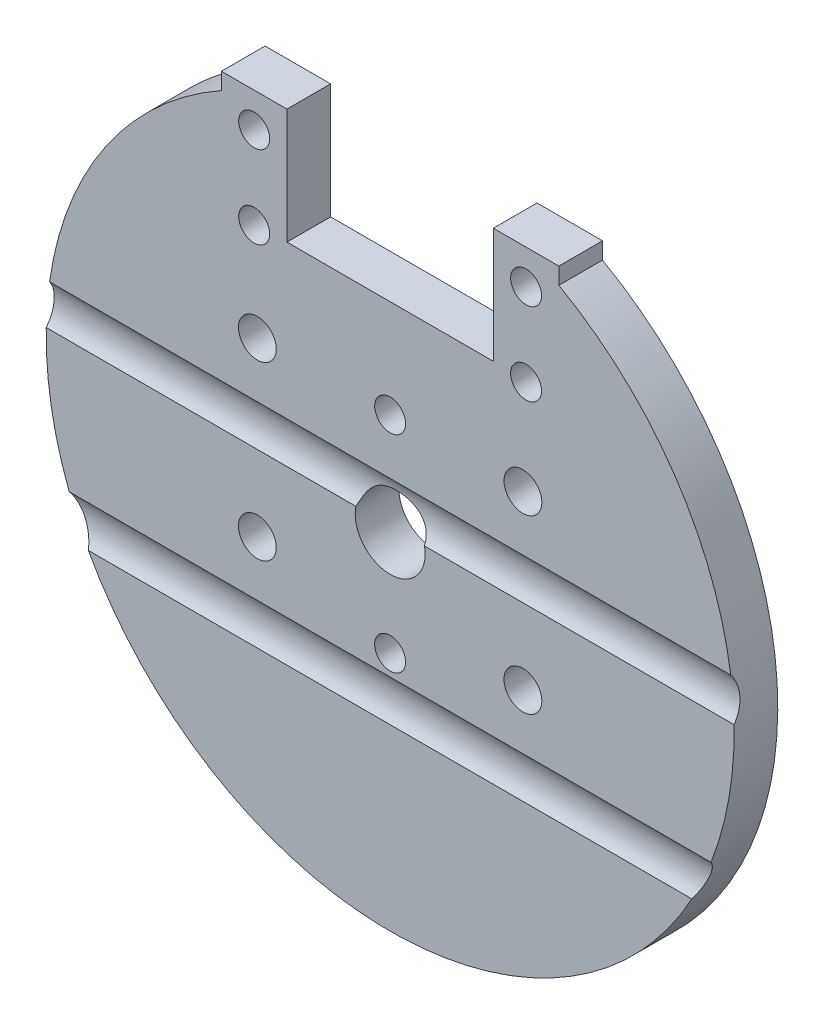
SolidWorks part; units mm, degrees
material "6061 Alloy"
ref_plane "Front Plane" through (0, 0, 0) normal (0, 0, 1) x (1, 0, 0)
ref_plane "Top Plane" through (0, 0, 0) normal (0, 1, 0) x (1, 0, 0)
ref_plane "Right Plane" through (0, 0, 0) normal (1, 0, 0) x (0, 0, -1)
sketch "Sketch1" plane through (0, 0, 0) normal (0, 0, 1) x (1, 0, 0)
  circle A0 centre (0, 0) radius 50
  dimension "D1" = 100
extrude "1/4" add sketch "Sketch1" along normal blind 6.35
sketch "Sketch2" plane through (0, 0, 6.35) normal (0, 0, 1) x (1, 0, 0)
  line L0 (0, 0) -> (0, 50) construction
  line L1 (-1.318, 74.311) -> (-1.318, 76.1424) construction
  line L3 (-15, 46) -> (-15, 29.25)
  line L4 (-15, 29.25) -> (15, 29.25)
  line L5 (15, 46) -> (15, 29.25)
  line L6 (0, 0) -> (0, 50) construction
  line L7 (-15, 37.625) -> (15, 37.625) construction
  line L8 (-30.7361, 76.1424) -> (28.1002, 76.1424)
  line L9 (-30.7361, 76.1424) -> (-30.7361, 46)
  line L10 (-30.7361, 46) -> (-15, 46)
  line L11 (28.1002, 76.1424) -> (28.1002, 46)
  line L12 (15, 46) -> (28.1002, 46)
  line L13 (-30.7361, 61.0712) -> (28.1002, 61.0712) construction
  circle A0 centre (0, 0) radius 50 construction
  point P6 (0, 37.625)
  point P130 (-1.318, 61.0712)
  dimension "D1" = 30
  dimension "D2" = 29.25
  dimension "D3" = 46
extrude "Cut-Extrude1" cut sketch "Sketch2" against normal up to surface (6.35 mm away) up to face at (50, 0, 0)
sketch "Sketch3" plane through (0, 0, 6.35) normal (0, 0, 1) x (1, 0, 0)
  line L1 (-15, 29.25) -> (-24.525, 29.25)
  line L2 (-15, 29.25) -> (-15, 46)
  line L3 (-15, 46) -> (-24.525, 46)
  line L4 (-24.525, 29.25) -> (-24.525, 46)
  line L5 (-19.7625, 46) -> (-19.7625, 29.25) construction
  line L6 (-15, 37.625) -> (-24.525, 37.625) construction
  line L7 (15, 29.25) -> (24.525, 29.25)
  line L8 (15, 29.25) -> (15, 46)
  line L9 (15, 46) -> (24.525, 46)
  line L10 (24.525, 29.25) -> (24.525, 46)
  line L11 (19.7625, 46) -> (19.7625, 29.25) construction
  line L12 (15, 37.625) -> (24.525, 37.625) construction
  point P168 (19.7625, 37.625)
  point P204 (-19.7625, 37.625)
  dimension "D1" = 9.525
  dimension "D2" = 9.525
  dimension "D3" = 46
extrude "Boss-Extrude2" add sketch "Sketch3" against normal up to surface (6.35 mm away) up to face at (0, 24.4167, 0)
sketch "Sketch4" plane through (0, 0, 6.35) normal (0, 0, 1) x (1, 0, 0)
  line L0 (-15, 35) -> (-24.525, 35) construction
  line L2 (-24.525, 46) -> (-24.525, 43.5721) construction
  line L3 (-19.7625, 41) -> (-19.7625, 35) construction
  line L4 (0, 0) -> (0, 50.3734) construction
  line L5 (-15, 46) -> (-15, 29.25) construction
  circle A0 centre (-19.7625, 41) radius 2.25
  circle A1 centre (-19.7625, 29) radius 2.25
  circle A2 centre (19.7625, 29) radius 2.25
  circle A3 centre (19.7625, 41) radius 2.25
  dimension "D1" = 4.5
  dimension "D2" = 6
  dimension "D3" = 35
extrude "M4_through" cut sketch "Sketch4" against normal up to surface (6.35 mm away) up to face at (0, 29.509, 0)
chamfer "Chamfer1" distance 2.5 angle 45 4 edges at (22.0125, 41, 0) (-17.5125, 29, 0) (-17.5125, 41, 0) (22.0125, 29, 0)
sketch "Sketch5" plane through (0, 0, 6.35) normal (0, 0, 1) x (1, 0, 0)
  circle A0 centre (0, 0) radius 5.08
  dimension "D1" = 10.16
extrude "Cut-Extrude2" cut sketch "Sketch5" against normal up to surface (6.35 mm away) up to face at (-15.0125, 29, 0)
sketch "Sketch6" plane through (0, 0, 6.35) normal (0, 0, 1) x (1, 0, 0)
  circle A0 centre (0, 0) radius 15 construction
  circle A1 centre (0, 15) radius 2.25
  circle A2 centre (0, -15) radius 2.25
  point P13 (0, 0)
  dimension "D1" = 30
  dimension "D2" = 4.5
  dimension "D3" = 2
extrude "M4_through2" cut sketch "Sketch6" against normal up to surface (6.35 mm away) up to face at (5.08, 0, 0)
sketch "Sketch7" plane through (0, 0, 6.35) normal (0, 0, 1) x (1, 0, 0)
  line L0 (0, 0) -> (0, 38.8961) construction
  line L1 (-19.3, 15) -> (-19.3, -10) construction
  circle A0 centre (-19.3, 15) radius 2.75
  circle A1 centre (-19.3, -10) radius 2.75
  circle A2 centre (19.3, -10) radius 2.75
  circle A3 centre (19.3, 15) radius 2.75
  circle A4 centre (0, 0) radius 30 construction
  point P11 (-19.3, 11.4777)
  dimension "D2" = 5.5
  dimension "D3" = 25
  dimension "D4" = 60
  dimension "D1" = 19.3
  dimension "D5" = 15
extrude "M5_through" cut sketch "Sketch7" against normal up to surface (6.35 mm away) up to face at (2.25, 15, 0)
sketch "Sketch8" plane through (0, 0, 0) normal (1, 0, 0) x (0, 0, -1)
  line L0 (-10.35, 4) -> (-6.35, 4) construction
  line L2 (-6.35, 43.5721) -> (-6.35, -50) construction
  line L4 (-10.35, -21) -> (-6.35, -21) construction
  line L6 (-10.35, 4) -> (-10.35, -21) construction
  line L7 (-6.35, 17.75) -> (-6.35, 12.25) construction
  circle A0 centre (-10.35, 4) radius 5
  circle A1 centre (-10.35, -21) radius 5
  point P4 (-6.35, 15)
  point P5 (0, 0)
  point P15 (0, 0)
  dimension "D1" = 10
  dimension "D2" = 4
  dimension "D3" = 11
  dimension "D4" = 25
extrude "Cut-Extrude4" cut sketch "Sketch8" against normal through all and the other way through all
